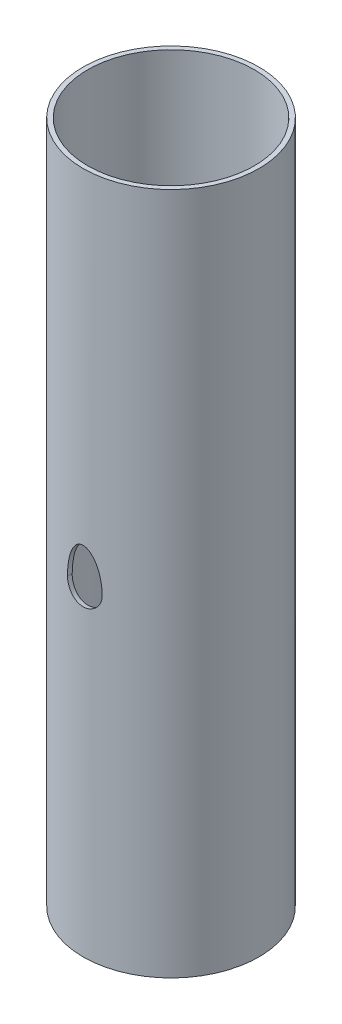
SolidWorks part; units mm, degrees
ref_plane "Front Plane" through (0, 0, 0) normal (0, 0, 1) x (1, 0, 0)
ref_plane "Top Plane" through (0, 0, 0) normal (0, 1, 0) x (1, 0, 0)
ref_plane "Right Plane" through (0, 0, 0) normal (1, 0, 0) x (0, 0, -1)
sketch "Sketch2" plane through (0, 0, 0) normal (0, 1, 0) x (1, 0, 0)
  circle A0 centre (0, 0) radius 36
  circle A1 centre (0, 0) radius 38
  dimension "D1" = 2
  dimension "D2" = 76
extrude "Boss-Extrude1" add sketch "Sketch2" along normal blind 295
ref_axis "Axis1" through (41.8, 0, 0) along (-1, 0, 0)
ref_plane "Plane1" through (0, 0, 0) normal (0, 0.2045, 0.9789) x (-1, 0, 0)
sketch "Sketch3" plane through (0, 0, 0) normal (0, 0.2045, 0.9789) x (-1, 0, 0)
  line L0 (0, 41.8) -> (0, -41.8) construction
  line L2 (-41.8, 0) -> (41.8, 0) construction
  arc A0 (7.5, -128) -> (-7.5, -128) centre (0, -128) ccw
  arc A1 (-7.5, -128) -> (7.5, -128) centre (0, -128) ccw construction
  ellipse E0 centre (0, -128) end of major axis (0, -143) minor radius 7.5 (-7.5, -128) -> (7.5, -128) ccw
  dimension "D1" = 15
  dimension "D2" = 128
  dimension "D3" = 15
extrude "Cut-Extrude1" cut sketch "Sketch3" along normal up to next
